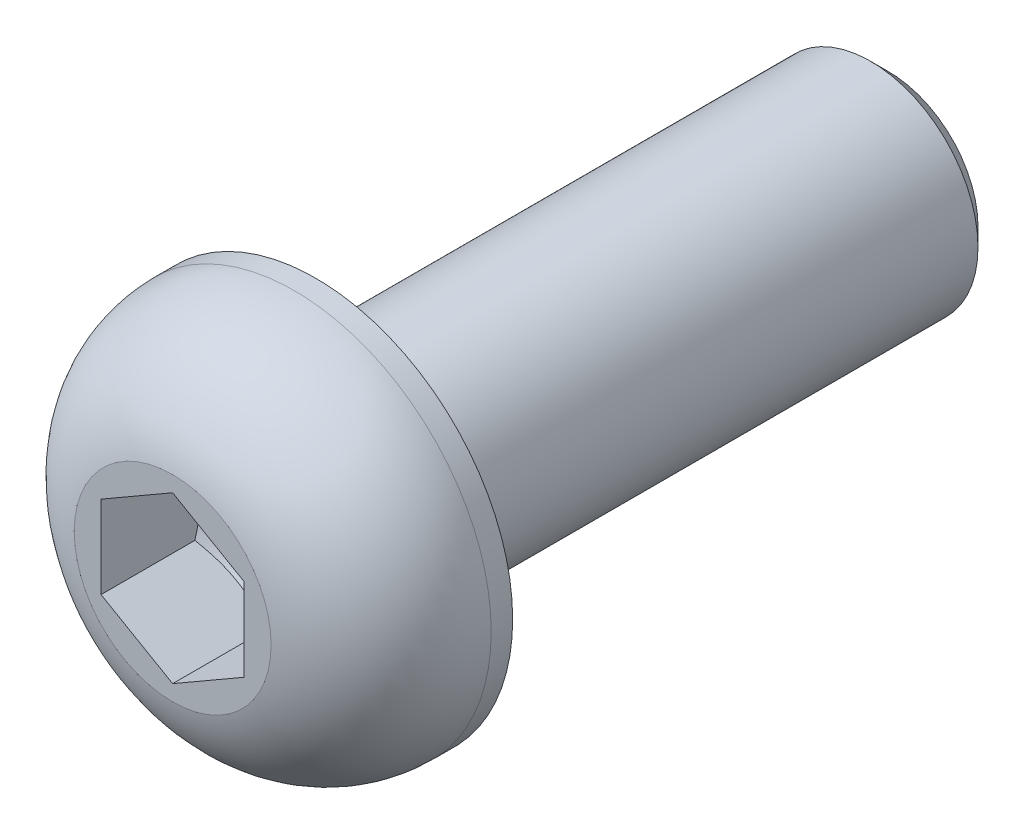
SolidWorks part; units mm, degrees
material "Stainless Steel (ferritic)"
ref_plane "Front" through (0, 0, 0) normal (0, 0, 1) x (1, 0, 0)
ref_plane "Top" through (0, 0, 0) normal (0, 1, 0) x (1, 0, 0)
ref_plane "Right" through (0, 0, 0) normal (1, 0, 0) x (0, 0, -1)
sketch "Sketch2" plane through (0, 0, 0) normal (1, 0, 0) x (0, 0, -1)
  line L0 (-14.7719, 0) -> (21.8061, 0) construction
  line L1 (8, 0) -> (8, 1.5)
  line L2 (8, 1.5) -> (0, 1.5)
  line L3 (0, 1.5) -> (0, 2.75)
  line L4 (0, 2.75) -> (-0.3, 2.75)
  line L5 (-2, 1.375) -> (-2, 0)
  line L6 (-2, 0) -> (8, 0)
  arc A0 (-0.3, 2.75) -> (-2, 1.375) centre (-0.3, 1.0116) ccw
  dimension "d" = 3
  dimension "Dk" = 5.5
  dimension "l" = 8
  dimension "l1" = 0.3
  dimension "K" = 2
  dimension "e" = 2.75
revolve "Revolve1" add sketch "Sketch2" angle 360 about L0
chamfer "Chamfer1" distance 0.25 angle 45 1 edges at (1.5, 0, -8)
sketch "Sketch3" plane through (0, 0, 0) normal (1, 0, 0) x (0, 0, -1)
  line L0 (-1.2619, 0) -> (-0.5017, 0) construction
  line L1 (-2, 0) -> (-2, 1)
  line L2 (-2, 1.375) -> (-2, -1.375) construction
  line L3 (-2, 1) -> (-0.6, 1)
  line L4 (-0.6, 1) -> (-0.0226, 0)
  line L5 (-0.0226, 0) -> (-2, 0)
  dimension "B" = 2
  dimension "D2" = 60
  dimension "m" = 1.4
revolve "Cut-Revolve1" cut sketch "Sketch3" angle 360 about L0
sketch "Sketch4" plane through (0, 0, 2) normal (0, 0, 1) x (1, 0, 0)
  line L1 (0, 1.1547) -> (-1, 0.5774)
  line L2 (-1, 0.5774) -> (-1, -0.5774)
  line L3 (-1, -0.5774) -> (0, -1.1547)
  line L4 (0, -1.1547) -> (1, -0.5774)
  line L5 (1, -0.5774) -> (1, 0.5774)
  line L6 (1, 0.5774) -> (0, 1.1547)
  circle A0 centre (0, 0) radius 1 construction
  circle A1 centre (0, 0) radius 1 construction
extrude "Cut-Extrude1" cut sketch "Sketch4" against normal up to surface (1.3107 mm away) up to face at (1, 0, 0.6)
equation "\"e@Sketch2\" = \"Dk@Sketch2\" / 2"
